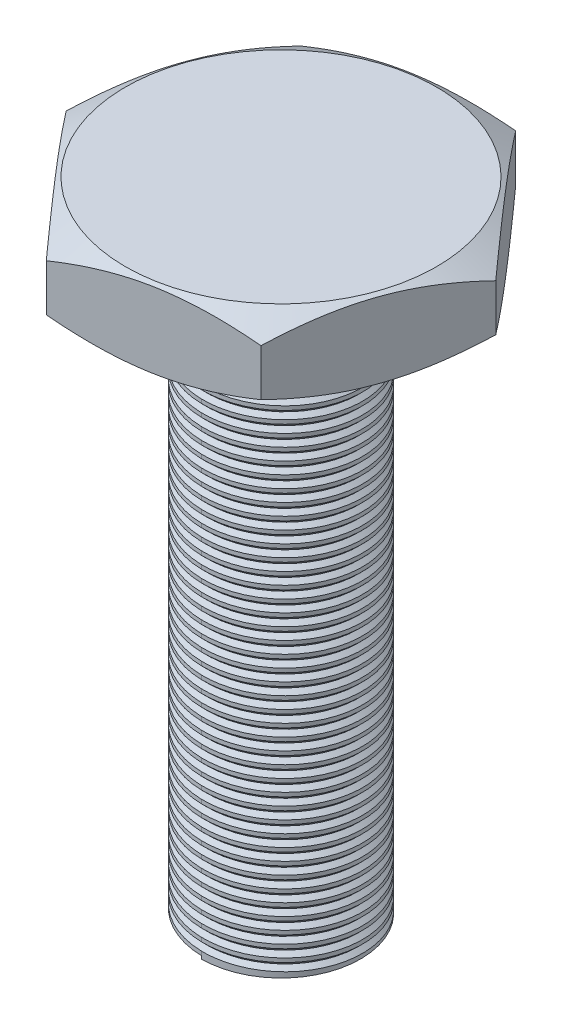
SolidWorks part; units mm, degrees
ref_plane "Спереди" through (0, 0, 0) normal (0, 0, 1) x (1, 0, 0)
ref_plane "Сверху" through (0, 0, 0) normal (0, 1, 0) x (1, 0, 0)
ref_plane "Справа" through (0, 0, 0) normal (1, 0, 0) x (0, 0, -1)
sketch "Эскиз7" plane through (0, 0, 0) normal (0, 1, 0) x (1, 0, 0)
  line L1 (-3.0059, 3.5069) -> (-4.54, -0.8497)
  line L2 (-4.54, -0.8497) -> (-1.5341, -4.3566)
  line L3 (-1.5341, -4.3566) -> (3.0059, -3.5069)
  line L4 (3.0059, -3.5069) -> (4.54, 0.8497)
  line L5 (4.54, 0.8497) -> (1.5341, 4.3566)
  line L6 (1.5341, 4.3566) -> (-3.0059, 3.5069)
  circle A0 centre (0, 0) radius 4 construction
extrude "Бобышка-Вытянуть1" add sketch "Эскиз7" along normal blind 2
sketch "Эскиз8" plane through (0, 2, 0) normal (0, 1, 0) x (1, 0, 0)
  circle A0 centre (0, 0) radius 3.9051
extrude "Вырез-Вытянуть1" cut sketch "Эскиз8" against normal blind 2 draft 60 flip side to cut
sketch "Эскиз9" plane through (0, 0, 0) normal (0, -1, 0) x (1, 0, 0)
  circle A0 centre (0, 0) radius 3.9051
extrude "Вырез-Вытянуть2" cut sketch "Эскиз9" against normal blind 2 draft 60 flip side to cut
sketch "Эскиз10" plane through (0, 0, 0) normal (0, -1, 0) x (1, 0, 0)
  circle A0 centre (0, 0) radius 2
extrude "Бобышка-Вытянуть2" add sketch "Эскиз10" along normal blind 14
sketch "Эскиз11" plane through (0, -14, 0) normal (0, -1, 0) x (1, 0, 0)
  circle A0 centre (0, 0) radius 2
curve "Спираль1" pitch 0.3 height 13.875 radius 2 left hand yes centre (0, -14, 0) axis (0, 1, 0) start towards (0, 0, 1)
sketch "Эскиз19" plane through (0, 0, 0) normal (0, 0, 1) x (1, 0, 0)
  line L0 (2, -12.1) -> (1.9, -12)
  line L1 (1.9, -12) -> (2, -11.9)
  line L2 (2, -11.9) -> (2, -12.1)
sweep "Вырез-По траектории10" cut profiles "Эскиз19" path "Спираль1"
